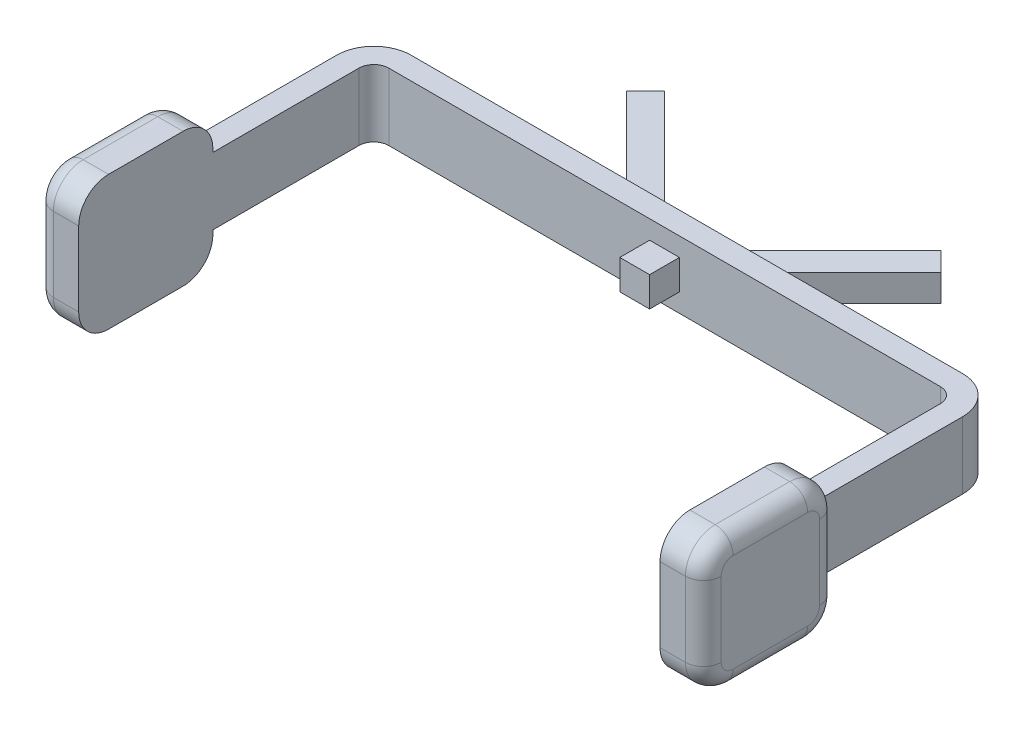
SolidWorks part; units mm, degrees
ref_plane "前视基准面" through (0, 0, 0) normal (0, 0, 1) x (1, 0, 0)
ref_plane "上视基准面" through (0, 0, 0) normal (0, 1, 0) x (1, 0, 0)
ref_plane "右视基准面" through (0, 0, 0) normal (1, 0, 0) x (0, 0, -1)
sketch "草图1" plane through (0, 0, 0) normal (0, 1, 0) x (1, 0, 0)
  line L0 (-1.5, 0) -> (1.5, 0)
  line L1 (1.5, 0) -> (9.2782, 7.7782)
  line L2 (-1.5, 0) -> (-9.2782, 7.7782)
  line L3 (-9.2782, 7.7782) -> (-10.551, 6.5054)
  line L4 (9.2782, 7.7782) -> (10.551, 6.5054)
  line L5 (-18.5, -1.5) -> (18.5, -1.5)
  line L6 (-1.5, -1.5) -> (1.5, -1.5) construction
  line L7 (-19.5, -2.5) -> (-19.5, -12.3)
  line L8 (19.5, -2.5) -> (19.5, -12.3)
  line L9 (-10.551, 6.5054) -> (-4.0456, 0)
  line L10 (10.551, 6.5054) -> (4.0456, 0)
  line L11 (-21, -2.5) -> (-21, -12.3)
  line L12 (-18.5, 0) -> (18.5, 0)
  line L13 (21, -2.5) -> (21, -12.3)
  line L14 (-21, -12.3) -> (-19.5, -12.3)
  line L15 (19.5, -12.3) -> (21, -12.3)
  line L16 (-1, -3.5) -> (-1, -1.5)
  line L17 (1, -3.5) -> (-1, -3.5)
  line L18 (1, -3.5) -> (1, -1.5)
  arc A0 (-18.5, -1.5) -> (-19.5, -2.5) centre (-18.5, -2.5) ccw
  arc A1 (19.5, -2.5) -> (18.5, -1.5) centre (18.5, -2.5) ccw
  arc A2 (-18.5, 0) -> (-21, -2.5) centre (-18.5, -2.5) ccw
  arc A3 (21, -2.5) -> (18.5, 0) centre (18.5, -2.5) ccw
  point P4 (0, 0)
  point P8 (0, 0)
  point P11 (0, 1.5)
  point P14 (-2.9, -1.5)
  point P16 (0, -1.5)
  point P20 (0, -4.3)
  point P22 (-19.5, -1.5)
  point P25 (19.5, -1.5)
  point P35 (0, 0)
  point P39 (1.5, 0)
  point P41 (0, -3.5)
  point P42 (0, 0)
  point P44 (16.6, -6.4973)
  dimension "D2" = 1
  dimension "D3" = 1
  dimension "D1" = 18.5
  dimension "D5" = 9.8
  dimension "D6" = 0
  dimension "D7" = 11
  dimension "D8" = 11
  dimension "D9" = 9.8
  dimension "D10" = 18.5
  dimension "D11" = 2
  dimension "D4" = 1.5
extrude "凸台-拉伸2" add sketch "草图1" along normal mid plane 4.5 contours L12 A3 L13 L15 L8 A1 L5 A0 L7 L14 L11 A2
extrude "凸台-拉伸3" add sketch "草图1<5>" along normal mid plane 2 contours L17 L18 L5 L16 region at (0, 0, 2.5)
sketch "草图1<5>" plane through (0, 0, 0) normal (0, 1, 0) x (1, 0, 0) same geometry as "草图1"
extrude "凸台-拉伸4" add sketch "草图1<6>" along normal mid plane 1.8 contours L1 L12 L10 L4 | L9 L12 L2 L3 region at (-6.3153, 0, -3.5803) region at (6.3153, 0, -3.5803)
sketch "草图1<6>" plane through (0, 0, 0) normal (0, 1, 0) x (1, 0, 0) same geometry as "草图1"
ref_plane "基准面1" through (19.5, 0, 0) normal (-1, 0, 0) x (0, 0, 1)
sketch "草图2" plane through (19.5, 0, 0) normal (-1, 0, 0) x (0, 0, 1)
  line L0 (12.3, 2.25) -> (12.3, -2.25) construction
  line L1 (12.3, 0) -> (16.8, -0.0211) construction
  line L2 (12.3, 2.25) -> (12.3, -2.25) construction
  line L3 (19.3, 4.4789) -> (14.3, 4.4789)
  line L4 (21.3, 2.4789) -> (21.3, -2.5211)
  line L5 (19.3, -4.5211) -> (14.3, -4.5211)
  line L6 (12.3, 2.4789) -> (12.3, -2.5211)
  line L7 (21.3, 4.4789) -> (12.3, -4.5211) construction
  line L8 (21.3, -4.5211) -> (12.3, 4.4789) construction
  arc A0 (14.3, 4.4789) -> (12.3, 2.4789) centre (14.3, 2.4789) ccw
  arc A1 (21.3, -2.5211) -> (19.3, -4.5211) centre (19.3, -2.5211) cw
  arc A2 (14.3, -4.5211) -> (12.3, -2.5211) centre (14.3, -2.5211) cw
  arc A3 (21.3, 2.4789) -> (19.3, 4.4789) centre (19.3, 2.4789) ccw
  dimension "D3" = 2
  dimension "D4" = 2
  dimension "D1" = 9
  dimension "D2" = 9
  dimension "D5" = 0
extrude "凸台-拉伸5" add sketch "草图2" against normal blind 2.9
fillet "圆角1" radius 1.2 8 edges at (22.4, -0.0211, 12.3) (22.4, -3.9353, 12.8858) (22.4, -4.5211, 16.8) (22.4, -3.9353, 20.7142) (22.4, -0.0211, 21.3) (22.4, 3.8931, 20.7142) (22.4, 4.4789, 16.8) (22.4, 3.8931, 12.8858)
mirror "镜向2" about plane through (0, 0, 0) normal (1, 0, 0) of "凸台-拉伸5", "圆角1"
